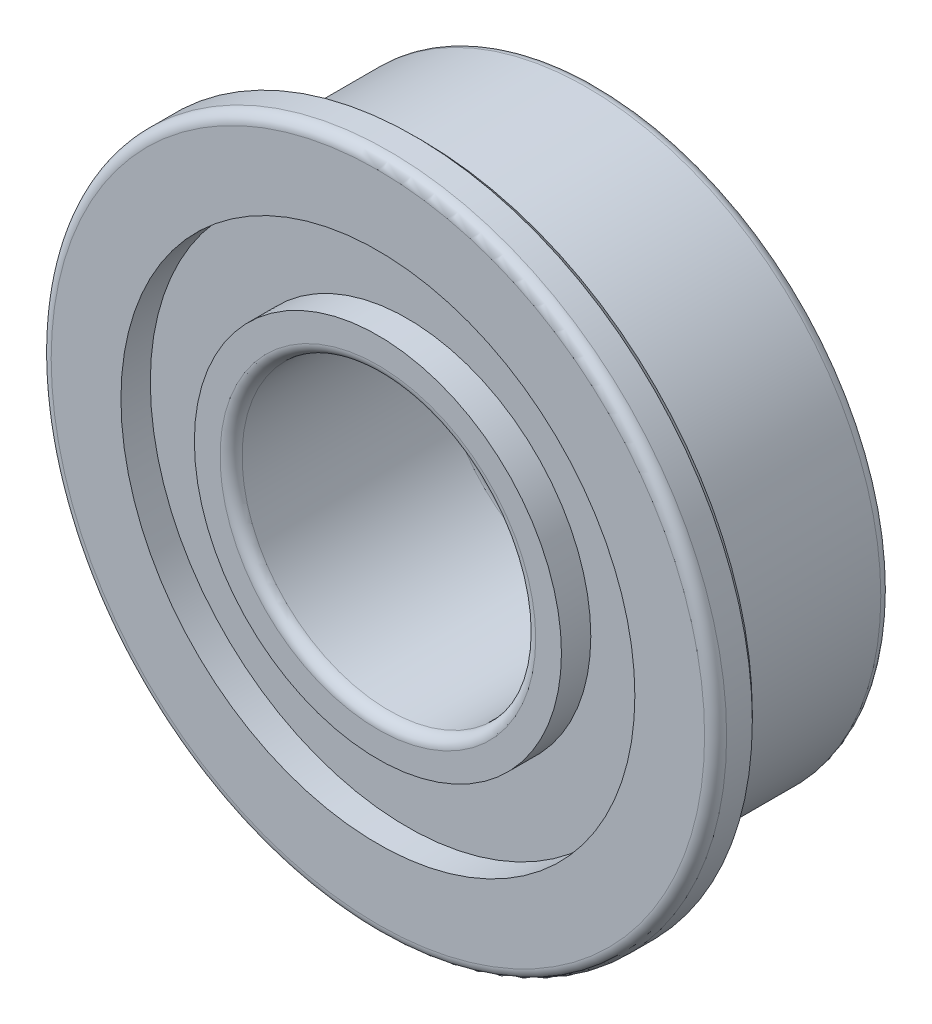
SolidWorks part; units mm, degrees
ref_plane "Front Plane" through (0, 0, 0) normal (0, 0, 1) x (1, 0, 0)
ref_plane "Top Plane" through (0, 0, 0) normal (0, 1, 0) x (1, 0, 0)
ref_plane "Right Plane" through (0, 0, 0) normal (1, 0, 0) x (0, 0, -1)
sketch "Sketch1" plane through (0, 0, 0) normal (0, 0, 1) x (1, 0, 0)
  circle A0 centre (0, 0) radius 2
  circle A1 centre (0, 0) radius 4
  dimension "D1" = 4
  dimension "D2" = 8
extrude "Boss-Extrude1" add sketch "Sketch1" along normal blind 3
sketch "Sketch2" plane through (0, 0, 3) normal (0, 0, 1) x (1, 0, 0)
  circle A0 centre (0, 0) radius 4.6
  circle A1 centre (0, 0) radius 4
  dimension "D1" = 9.2
extrude "Boss-Extrude2" add sketch "Sketch2" against normal blind 0.6
sketch "Sketch3" plane through (0, 0, 0) normal (0, 0, -1) x (-1, 0, 0)
  circle A0 centre (0, 0) radius 2.5
  circle A1 centre (0, 0) radius 3.5
  dimension "D1" = 5
  dimension "D2" = 7
extrude "Cut-Extrude1" cut sketch "Sketch3" against normal blind 0.2
extrude "Cut-Extrude2" cut sketch "Sketch3<2>" along normal blind 0.4 from surface starting at face at (2, 0, 3)
sketch "Sketch3<2>" plane through (0, 0, 0) normal (0, 0, -1) x (-1, 0, 0) same geometry as "Sketch3"
fillet "Fillet1" radius 0.15 5 edges at (4, 0, 0) (2, 0, 0) (2, 0, 3) (4.6, 0, 3) (-2.5, 0, 0)
chamfer "Chamfer1" distance 0.1 angle 45 1 edges at (4.6, 0, 2.4)
